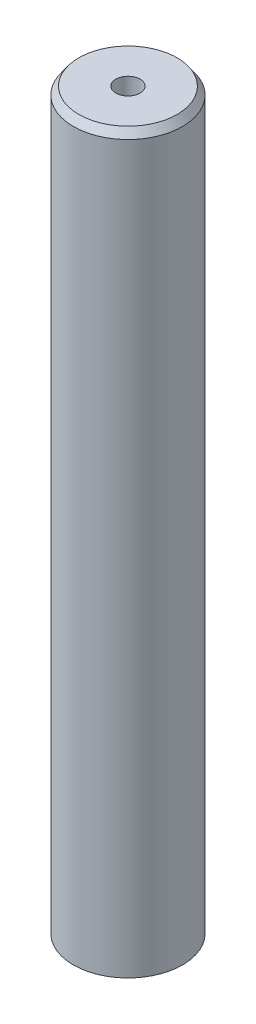
SolidWorks part; units mm, degrees
ref_plane "Front Plane" through (0, 0, 0) normal (0, 0, 1) x (1, 0, 0)
ref_plane "Top Plane" through (0, 0, 0) normal (0, 1, 0) x (1, 0, 0)
ref_plane "Right Plane" through (0, 0, 0) normal (1, 0, 0) x (0, 0, -1)
sketch "Sketch1" plane through (0, 0, 0) normal (0, 1, 0) x (1, 0, 0)
  circle A0 centre (0, 0) radius 7.5
  dimension "SHAFT_OD" = 15
extrude "Boss-Extrude1" add sketch "Sketch1" along normal blind 101.5986
sketch "Sketch2" plane through (0, 0, 0) normal (0, 1, 0) x (1, 0, 0)
  circle A0 centre (0, 0) radius 1.6666
  dimension "BORE_D" = 3.3332
extrude "Cut-Extrude1" cut sketch "Sketch2" along normal through all
chamfer "Chamfer1" distance 1.0594 angle 35.235 2 edges at (0, 101.5986, 7.5) (0, 0, 7.5) first distance on face at (0, 101.5986, 7.5) first distance on face at (0, 0, 1.6666)
